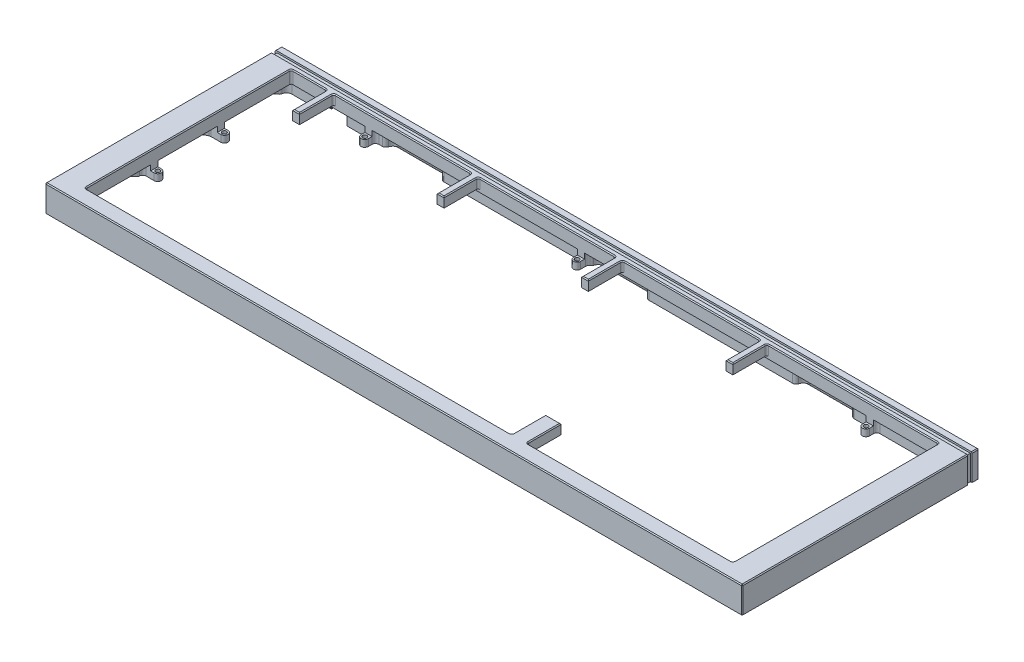
SolidWorks part; units mm, degrees
material "6061-T6 (SS)"
ref_plane "Front Plane" through (0, 0, 0) normal (0, 0, 1) x (1, 0, 0)
ref_plane "Top Plane" through (0, 0, 0) normal (0, 1, 0) x (1, 0, 0)
ref_plane "Right Plane" through (0, 0, 0) normal (1, 0, 0) x (0, 0, -1)
sketch "Sketch1" plane through (0, 0, 0) normal (0, 1, 0) x (1, 0, 0)
  line L1 (0, 0) -> (390.7, 0)
  line L2 (0, 0) -> (0, 132.7)
  line L3 (0, 132.7) -> (390.7, 132.7)
  line L4 (390.7, 0) -> (390.7, 132.7)
  line L5 (13.9, 124) -> (376.8, 124)
  line L6 (13.9, 124) -> (13.9, 8.7)
  line L7 (13.9, 8.7) -> (376.8, 8.7)
  line L8 (376.8, 124) -> (376.8, 8.7)
  point P9 (195.35, 124)
  point P10 (195.35, 132.7)
  point P11 (13.9, 66.35)
  point P12 (0, 66.35)
  dimension "D1" = 362.9
  dimension "D2" = 115.3
  dimension "D3" = 8.7
  dimension "D4" = 13.9
extrude "Main Body" add sketch "Sketch1" along normal blind 14.8
sketch "Sketch2" plane through (0, 0, 0) normal (0, -1, 0) x (1, 0, 0)
  line L0 (390.7, -132.7) -> (0, -132.7) construction
  line L1 (388.7, -130.7) -> (2, -130.7)
  line L2 (388.7, -130.7) -> (388.7, -2)
  line L3 (388.7, -2) -> (2, -2)
  line L4 (2, -130.7) -> (2, -2)
  line L5 (390.7, 0) -> (390.7, -132.7) construction
  point P4 (195.35, -130.7)
  point P7 (195.35, -132.7)
  point P8 (388.7, -66.35)
  point P11 (390.7, -66.35)
  dimension "D1" = 2
  dimension "D2" = 2
extrude "Alignment Guide" cut sketch "Sketch2" against normal blind 1 contours L2 L1 L4 L3
sketch "Sketch3" plane through (0, 14.8, 0) normal (0, 1, 0) x (1, 0, 0)
  line L0 (13.9, 8.7) -> (376.8, 8.7) construction
  line L1 (252.8, 27.8) -> (261.5, 27.8)
  line L2 (252.8, 27.8) -> (252.8, 8.7)
  line L3 (252.8, 8.7) -> (261.5, 8.7)
  line L4 (261.5, 27.8) -> (261.5, 8.7)
  line L5 (376.8, 8.7) -> (376.8, 124) construction
  line L6 (376.8, 124) -> (13.9, 124) construction
  line L7 (33.9, 124) -> (37.7, 124)
  line L8 (33.9, 124) -> (33.9, 104.9)
  line L9 (33.9, 104.9) -> (37.7, 104.9)
  line L10 (37.7, 124) -> (37.7, 104.9)
  line L11 (13.9, 124) -> (13.9, 8.7) construction
  line L12 (114.9, 124) -> (118.7, 124)
  line L13 (114.9, 124) -> (114.9, 104.9)
  line L14 (114.9, 104.9) -> (118.7, 104.9)
  line L15 (118.7, 124) -> (118.7, 104.9)
  line L16 (195.8, 124) -> (199.6, 124)
  line L17 (195.8, 124) -> (195.8, 104.9)
  line L18 (195.8, 104.9) -> (199.6, 104.9)
  line L19 (199.6, 124) -> (199.6, 104.9)
  line L20 (276.8, 124) -> (280.6, 124)
  line L21 (276.8, 124) -> (276.8, 104.9)
  line L22 (276.8, 104.9) -> (280.6, 104.9)
  line L23 (280.6, 124) -> (280.6, 104.9)
  point P8 (257.15, 8.7)
  dimension "D1" = 115.3
  dimension "D2" = 124
  dimension "D3" = 19.1
  dimension "D4" = 3.8
  dimension "D5" = 19.1
  dimension "D6" = 77.2
  dimension "D7" = 77.1
  dimension "D8" = 77.2
  dimension "D9" = 20
extrude "Blockers" add sketch "Sketch3" against normal blind 5.5
fillet "Fillet5" radius 1 14 edges at (280.6, 12.05, -124) (276.8, 12.05, -124) (195.8, 12.05, -124) (199.6, 12.05, -124) (118.7, 12.05, -124) (114.9, 12.05, -124) (33.9, 12.05, -124) (37.7, 12.05, -124) (13.9, 7.9, -124) (13.9, 7.9, -8.7) (252.8, 12.05, -8.7) (261.5, 12.05, -8.7) (376.8, 7.9, -8.7) (376.8, 7.9, -124)
sketch "Sketch4" plane through (0, 1, 0) normal (0, -1, 0) x (1, 0, 0)
  line L0 (0, 0) -> (390.7, 0) construction
  line L1 (381.25, -125.9) -> (9.45, -125.9)
  line L2 (381.25, -125.9) -> (381.25, -6.8)
  line L3 (381.25, -6.8) -> (9.45, -6.8)
  line L4 (9.45, -125.9) -> (9.45, -6.8)
  line L5 (390.7, 0) -> (390.7, -132.7) construction
  point P4 (195.35, -6.8)
  point P7 (195.35, 0)
  point P8 (381.25, -66.35)
  point P11 (390.7, -66.35)
  dimension "D1" = 119.1
  dimension "D2" = 371.8
extrude "PCB Cutout" cut sketch "Sketch4" against normal offset from surface (6.8 mm away) 7 up to face at (195.35, 14.8, -66.35)
fillet "Fillet4" radius 3 8 edges at (9.45, 4.4, -6.8) (9.45, 4.4, -125.9) (381.25, 4.4, -125.9) (381.25, 4.4, -6.8) (2, 0.5, -130.7) (2, 0.5, -2) (388.7, 0.5, -2) (388.7, 0.5, -130.7)
sketch "Sketch6" plane through (0, 1, 0) normal (0, -1, 0) x (1, 0, 0)
  line L0 (381.25, -9.8) -> (381.25, -122.9) construction
  line L1 (307.3, -127.1) -> (313.4, -127.1)
  line L2 (307.3, -127.1) -> (307.3, -125.9)
  line L3 (307.3, -125.9) -> (313.4, -125.9)
  line L4 (313.4, -127.1) -> (313.4, -125.9)
  line L5 (12.45, -125.9) -> (378.25, -125.9) construction
  line L11 (378.25, -6.8) -> (12.45, -6.8) construction
  line L16 (328.4, -6.8) -> (322.3, -6.8)
  line L17 (328.4, -6.8) -> (328.4, -4.8)
  line L18 (328.4, -4.8) -> (322.3, -4.8)
  line L19 (322.3, -6.8) -> (322.3, -4.8)
  line L20 (378.25, -125.9) -> (12.45, -125.9) construction
  line L21 (0, 0) -> (390.7, 0) construction
  line L22 (198.4, -127.1) -> (192.32, -127.1)
  line L23 (198.4, -127.1) -> (198.4, -125.9)
  line L24 (390.7, -66.35) -> (195.35, -66.35) construction
  line L25 (390.7, 0) -> (390.7, -132.7) construction
  line L26 (328.6755, -66.35) -> (328.6755, -130.7) construction
  line L27 (385.7, -130.7) -> (5, -130.7) construction
  line L28 (328.6755, -66.35) -> (328.6755, -8.7) construction
  line L29 (375.8, -8.7) -> (14.9, -8.7) construction
  line L53 (198.4, -125.9) -> (192.32, -125.9)
  line L54 (192.32, -127.1) -> (192.32, -125.9)
  line L55 (390.7, -132.7) -> (0, -132.7) construction
  line L56 (195.35, -132.7) -> (195.35, 0) construction
  line L57 (68.4, -6.8) -> (68.4, -4.8)
  line L58 (62.3, -4.8) -> (68.4, -4.8)
  line L59 (62.3, -6.8) -> (62.3, -4.8)
  line L60 (62.3, -6.8) -> (68.4, -6.8)
  line L61 (77.3, -127.1) -> (77.3, -125.9)
  line L62 (83.4, -125.9) -> (77.3, -125.9)
  line L63 (83.4, -127.1) -> (83.4, -125.9)
  line L64 (83.4, -127.1) -> (77.3, -127.1)
  line L65 (12.45, -6.8) -> (378.25, -6.8) construction
  line L66 (192.3, -4.8) -> (198.42, -4.8)
  line L67 (192.3, -4.8) -> (192.3, -6.8)
  line L68 (192.3, -6.8) -> (198.42, -6.8)
  line L69 (198.42, -4.8) -> (198.42, -6.8)
  line L70 (378.25, -6.8) -> (12.45, -6.8) construction
  line L75 (381.25, -122.9) -> (381.25, -9.8) construction
  line L76 (325.85, -125.9) -> (294.85, -125.9)
  line L77 (325.85, -125.9) -> (325.85, -130.15)
  line L78 (325.85, -130.15) -> (294.85, -130.15)
  line L79 (294.85, -125.9) -> (294.85, -130.15)
  line L80 (381.25, -122.35) -> (384.3, -122.35)
  line L81 (381.25, -122.35) -> (381.25, -90.35)
  line L82 (381.25, -90.35) -> (384.3, -90.35)
  line L83 (384.3, -122.35) -> (384.3, -90.35)
  line L84 (64.85, -130.15) -> (95.85, -130.15)
  line L85 (381.25, -10.35) -> (384.3, -10.35)
  line L86 (381.25, -10.35) -> (381.25, -42.35)
  line L87 (381.25, -42.35) -> (384.3, -42.35)
  line L88 (384.3, -10.35) -> (384.3, -42.35)
  line L89 (210.85, -125.9) -> (179.85, -125.9)
  line L90 (210.85, -125.9) -> (210.85, -130.15)
  line L91 (210.85, -130.15) -> (179.85, -130.15)
  line L92 (179.85, -125.9) -> (179.85, -130.15)
  line L97 (95.85, -125.9) -> (95.85, -130.15)
  line L98 (64.85, -125.9) -> (95.85, -125.9)
  line L99 (64.85, -125.9) -> (64.85, -130.15)
  line L100 (210.85, -125.9) -> (210.85, -130.15)
  line L101 (179.85, -125.9) -> (179.85, -130.15)
  line L102 (340.85, -6.8) -> (309.85, -6.8)
  line L108 (9.45, -42.35) -> (6.4, -42.35)
  line L109 (6.4, -10.35) -> (6.4, -42.35)
  line L110 (9.45, -10.35) -> (6.4, -10.35)
  line L111 (9.45, -10.35) -> (9.45, -42.35)
  line L112 (9.45, -90.35) -> (6.4, -90.35)
  line L113 (6.4, -122.35) -> (6.4, -90.35)
  line L114 (9.45, -122.35) -> (6.4, -122.35)
  line L115 (9.45, -122.35) -> (9.45, -90.35)
  line L116 (340.85, -6.8) -> (340.85, -2)
  line L117 (340.85, -2) -> (309.85, -2)
  line L118 (309.85, -6.8) -> (309.85, -2)
  line L119 (385.7, -2) -> (5, -2) construction
  line L120 (385.7, -2) -> (5, -2) construction
  line L121 (210.85, -6.8) -> (179.85, -6.8)
  line L122 (210.85, -6.8) -> (210.85, -2)
  line L123 (210.85, -2) -> (179.85, -2)
  line L124 (179.85, -6.8) -> (179.85, -2)
  line L125 (379.85, -49.5312) -> (374.82, -49.5312) construction
  line L126 (80.85, -6.8) -> (49.85, -6.8)
  line L127 (80.85, -6.8) -> (80.85, -2)
  line L128 (80.85, -2) -> (49.85, -2)
  line L129 (49.85, -6.8) -> (49.85, -2)
  line L130 (377.0547, -82.3692) -> (384.3, -82.3692)
  line L131 (377.0547, -82.3692) -> (377.0547, -49.5312)
  line L132 (377.0547, -49.5312) -> (384.3, -49.5312)
  line L133 (384.3, -82.3692) -> (384.3, -49.5312)
  line L134 (13.6453, -49.5312) -> (6.4, -49.5312)
  line L135 (6.4, -82.3692) -> (6.4, -49.5312)
  line L136 (13.6453, -82.3692) -> (6.4, -82.3692)
  line L137 (13.6453, -82.3692) -> (13.6453, -49.5312)
  line L138 (379.85, -82.3692) -> (374.82, -82.3692) construction
  circle A0 centre (381.25, -106.35) radius 3.05
  circle A1 centre (381.25, -26.35) radius 3.05
  circle A2 centre (325.35, -4.8) radius 3.05
  circle A3 centre (310.35, -127.1) radius 3.05
  circle A8 centre (65.35, -4.8) radius 3.05
  circle A9 centre (9.45, -26.35) radius 3.05
  circle A10 centre (9.45, -106.35) radius 3.05
  circle A11 centre (80.35, -127.1) radius 3.05
  circle A12 centre (195.35, -127.1) radius 3.05
  circle A13 centre (195.35, -4.8) radius 3.05
  point P25 (195.35, -66.35)
  point P93 (384.3, -26.35)
  point P94 (384.3, -106.35)
  point P95 (310.35, -130.15)
  point P100 (195.35, -130.15)
  point P102 (325.35, -2)
  point P113 (195.35, -2)
  point P126 (65.35, -2)
  dimension "D4" = 6.1
  dimension "D5" = 115
  dimension "D8" = 6.1
  dimension "D1" = 40
  dimension "D2" = 4.8
  dimension "D3" = 40
  dimension "D6" = 0
  dimension "D7" = 5.6
  dimension "D9" = 130
  dimension "D10" = 32
  dimension "D11" = 31
sketch "Sketch9" plane through (0, 0, -132.7) normal (0, 0, -1) x (-1, 0, 0)
  line L1 (-41.8, 0) -> (-29.8, 0)
  line L2 (-41.8, 0) -> (-41.8, 3.2)
  line L3 (-41.8, 3.2) -> (-29.8, 3.2)
  line L4 (-29.8, 0) -> (-29.8, 3.2)
  line L5 (-390.7, 0) -> (0, 0) construction
  line L7 (0, 14.8) -> (0, 0) construction
  point P6 (-35.8, 3.2)
  dimension "D1" = 3.2
  dimension "D3" = 12
  dimension "D4" = 35.8
extrude "USB Cutout" cut sketch "Sketch9" against normal up to surface (8.7 mm away) up to face at (164.87, 11.9, -124)
sketch "Sketch11" plane through (0, 0, -125.9) normal (0, 0, 1) x (1, 0, 0)
  line L0 (378.25, 7.8) -> (12.45, 7.8) construction
  line L1 (43.3, 1) -> (28.3, 1)
  line L2 (43.3, 1) -> (43.3, 7.8)
  line L3 (43.3, 7.8) -> (28.3, 7.8)
  line L4 (28.3, 1) -> (28.3, 7.8)
  line L7 (12.45, 1) -> (29.8, 1) construction
  line L8 (29.8, 3.2) -> (41.8, 3.2) construction
  point P8 (35.8, 1)
  point P18 (35.8, 3.2)
  dimension "D1" = 15
extrude "PCB Clearance" cut sketch "Sketch11" against normal blind 3.9
fillet "Fillet7" radius 2.5 2 edges at (28.3, 4.4, -129.8) (43.3, 4.4, -129.8)
chamfer "Chamfer1" distance 0.5 46 edges at (14.1929, 14.8, -8.9929) (133.35, 14.8, -8.7) (252.5071, 14.8, -8.9929) (252.8, 14.8, -18.75) (257.15, 14.8, -27.8) (261.5, 14.8, -18.75) (261.7929, 14.8, -8.9929) (319.15, 14.8, -8.7) (376.5071, 14.8, -8.9929) (376.8, 14.8, -66.35) (376.5071, 14.8, -123.7071) (328.7, 14.8, -124) (280.8929, 14.8, -123.7071) (280.6, 14.8, -113.95) (278.7, 14.8, -104.9) (276.8, 14.8, -113.95) (276.5071, 14.8, -123.7071) (238.2, 14.8, -124) (199.8929, 14.8, -123.7071) (199.6, 14.8, -113.95) (197.7, 14.8, -104.9) (195.8, 14.8, -113.95) (195.5071, 14.8, -123.7071) (157.25, 14.8, -124) (118.9929, 14.8, -123.7071) (118.7, 14.8, -113.95) (116.8, 14.8, -104.9) (114.9, 14.8, -113.95) (114.6071, 14.8, -123.7071) (76.3, 14.8, -124) (37.9929, 14.8, -123.7071) (37.7, 14.8, -113.95) (35.8, 14.8, -104.9) (33.9, 14.8, -113.95) (33.6071, 14.8, -123.7071) (23.9, 14.8, -124) (14.1929, 14.8, -123.7071) (13.9, 14.8, -66.35) (195.35, 14.8, -132.7) (390.7, 14.8, -66.35) (195.35, 14.8, 0) (0, 14.8, -66.35) (390.7, 7.4, -132.7) (390.7, 7.4, 0) (0, 7.4, -132.7) (0, 7.4, 0)
chamfer "Chamfer2" distance 0.1 5 edges at (390.7, 0, -66.35) (195.35, 0, 0) (0, 0, -66.35) (15.15, 0, -132.7) (216, 0, -132.7)
sketch "Sketch27" plane through (0, 14.8, 0) normal (0, 1, 0) x (1, 0, 0)
  line L0 (0, 0.5) -> (0, 132.2) construction
  line L1 (0, 128.95) -> (390.7, 128.95)
  line L2 (0, 128.95) -> (0, 126.45)
  line L3 (0, 126.45) -> (390.7, 126.45)
  line L4 (390.7, 128.95) -> (390.7, 126.45)
  line L5 (390.7, 132.2) -> (390.7, 0.5) construction
  line L6 (372.9261, 132.2) -> (372.9261, 124.5) construction
  line L7 (390.2, 132.2) -> (0.5, 132.2) construction
  line L9 (281.6, 124.5) -> (375.8, 124.5) construction
  point P14 (390.7, 127.7)
  dimension "D1" = 2.5
  dimension "D2" = 3.2
extrude "Cut-Extrude11" cut sketch "Sketch27" against normal blind 1
sketch "Sketch28" plane through (0, 13.8, 0) normal (0, 1, 0) x (1, 0, 0)
  line L1 (0, 128.95) -> (1, 128.95)
  line L2 (0, 128.95) -> (0, 126.45)
  line L3 (0, 126.45) -> (1, 126.45)
  line L4 (1, 128.95) -> (1, 126.45)
  line L5 (389.7, 128.95) -> (390.7, 128.95)
  line L6 (389.7, 128.95) -> (389.7, 126.45)
  line L7 (389.7, 126.45) -> (390.7, 126.45)
  line L8 (390.7, 128.95) -> (390.7, 126.45)
  line L9 (390.7, 128.95) -> (0, 128.95) construction
  line L10 (0, 126.45) -> (390.7, 126.45) construction
  dimension "D1" = 1
  dimension "D2" = 1
extrude "Cut-Extrude12" cut sketch "Sketch28" against normal through all
sketch "Sketch21" [suppressed] plane through (0, 14.8, 0) normal (0, 1, 0) x (1, 0, 0)
  line L0 (0.5, 132.7) -> (390.24, 132.7) construction
  line L1 (382.53, 132.7) -> (385.03, 132.7)
  line L2 (382.53, 132.7) -> (382.53, 72.7)
  line L3 (382.53, 72.7) -> (385.03, 72.7)
  line L4 (385.03, 132.7) -> (385.03, 72.7)
  line L5 (390.74, 132.2) -> (390.74, 129.7) construction
  line L6 (390.74, 129.1) -> (294.74, 129.1)
  line L7 (390.74, 129.1) -> (390.74, 127.6)
  line L8 (390.74, 127.6) -> (294.74, 127.6)
  line L9 (294.74, 129.1) -> (294.74, 127.6)
  line L10 (362.9081, 132.2) -> (362.9081, 124.5) construction
  line L11 (390.24, 132.2) -> (0.5, 132.2) construction
  line L12 (281.62, 124.5) -> (375.82, 124.5) construction
  line L13 (365.5702, 129.1) -> (365.5702, 127.6) construction
  line L14 (377.32, 119.5259) -> (390.24, 119.5259) construction
  line L15 (377.32, 123) -> (377.32, 9.7) construction
  line L16 (390.24, 0.5) -> (390.24, 127.2) construction
  line L17 (382.53, 116.0504) -> (385.03, 116.0504) construction
  point P28 (383.78, 116.0504)
  point P29 (383.78, 119.5259)
  point P30 (365.5702, 128.35)
  point P31 (362.9081, 128.35)
  dimension "D1" = 2.5
  dimension "D2" = 1.5
  dimension "D3" = 60
  dimension "D4" = 96
extrude "Cut-Extrude5" [suppressed] cut sketch "Sketch21" against normal blind 1 contours L4 L3 L2 L1 | L8 L9 L6 L7
sketch "Sketch23" [suppressed] plane through (390.74, 0, 0) normal (1, 0, 0) x (0, 0, -1)
  line L0 (129.1, 13.8) -> (129.1, 14.3) construction
  line L1 (127.6, 13.8) -> (129.1, 13.8)
  line L2 (127.6, 13.8) -> (127.6, 0)
  line L3 (127.6, 0) -> (129.1, 0)
  line L4 (129.1, 13.8) -> (129.1, 0)
extrude "Cut-Extrude6" [suppressed] cut sketch "Sketch23" against normal blind 1
sketch "Sketch19" plane through (0, 14.8, 0) normal (0, 1, 0) x (1, 0, 0)
  line L0 (0.5, 132.7) -> (390.2, 132.7) construction
  line L1 (5.45, 132.7) -> (8.45, 132.7)
  line L2 (5.45, 132.7) -> (5.45, 0)
  line L3 (5.45, 0) -> (8.45, 0)
  line L4 (8.45, 132.7) -> (8.45, 0)
  line L7 (382.25, 132.7) -> (385.25, 132.7)
  line L8 (382.25, 132.7) -> (382.25, 0)
  line L9 (382.25, 0) -> (385.25, 0)
  line L10 (385.25, 132.7) -> (385.25, 0)
  line L11 (390.2, 0) -> (0.5, 0) construction
  line L12 (377.3, 110.209) -> (390.2, 110.209) construction
  line L13 (377.3, 123) -> (377.3, 9.7) construction
  line L14 (390.2, 0.5) -> (390.2, 126.45) construction
  line L15 (382.25, 106.8719) -> (385.25, 106.8719) construction
  line L16 (0.5, 106.8719) -> (13.4, 106.8719) construction
  line L17 (0.5, 132.2) -> (0.5, 128.95) construction
  line L18 (13.4, 9.7) -> (13.4, 123) construction
  line L19 (5.45, 102.7297) -> (8.45, 102.7297) construction
  point P12 (383.75, 106.8719)
  point P14 (383.75, 110.209)
  point P30 (6.95, 102.7297)
  point P31 (6.95, 106.8719)
  dimension "D1" = 3
  dimension "D2" = 3
extrude "Cut-Extrude3" [suppressed] cut sketch "Sketch19" against normal blind 1
sketch "Sketch17" plane through (0, 14.8, 0) normal (0, 1, 0) x (1, 0, 0)
  line L0 (390.2, 0.5) -> (390.2, 126.45) construction
  line L1 (5.7, 129.6) -> (385, 129.6)
  line L2 (5.7, 129.6) -> (5.7, -2.65)
  line L3 (5.7, -2.65) -> (385, -2.65)
  line L4 (385, 129.6) -> (385, -2.65)
  line L5 (8.2, 127.1) -> (382.5, 127.1)
  line L6 (8.2, 127.1) -> (8.2, -0.15)
  line L7 (8.2, -0.15) -> (382.5, -0.15)
  line L8 (382.5, 127.1) -> (382.5, -0.15)
  line L9 (390.2, 132.2) -> (0.5, 132.2) construction
  line L10 (21.2533, 132.2) -> (21.2533, 124.5) construction
  line L11 (14.9, 124.5) -> (32.9, 124.5) construction
  line L12 (25.2757, 129.6) -> (25.2757, 127.1) construction
  line L13 (0.5, 116.1326) -> (13.4, 116.1326) construction
  line L14 (0.5, 132.2) -> (0.5, 128.95) construction
  line L15 (13.4, 9.7) -> (13.4, 123) construction
  line L16 (5.7, 120.1548) -> (8.2, 120.1548) construction
  point P8 (382.5, 63.475)
  point P9 (385, 63.475)
  point P12 (390.2, 63.475)
  point P13 (195.35, 129.6)
  point P14 (195.35, 127.1)
  point P17 (195.35, 132.2)
  point P24 (25.2757, 128.35)
  point P25 (21.2533, 128.35)
  point P34 (6.95, 116.1326)
  point P35 (6.95, 120.1548)
  dimension "D1" = 2.5
  dimension "D2" = 2.5
extrude "Cut-Extrude1" [suppressed] cut sketch "Sketch17" against normal blind 1
fillet "Fillet8" radius 0.1 9 edges at (213.75, 0, -130.7) (387.8213, 0, -129.8213) (17.4, 0, -130.7) (2.8787, 0, -129.8213) (2, 0, -66.35) (2.8787, 0, -2.8787) (195.35, 0, -2) (387.8213, 0, -2.8787) (388.7, 0, -66.35)
sketch "Sketch32" plane through (0, 1, 0) normal (0, -1, 0) x (1, 0, 0)
  line L0 (378.25, -125.9) -> (43.3, -125.9) construction
  line L3 (378.25, -125.9) -> (43.3, -125.9) construction
  line L4 (340.2441, -121.9) -> (336.2441, -121.9)
  line L5 (340.2441, -121.9) -> (340.2441, -125.9)
  line L6 (340.2441, -125.9) -> (336.2441, -125.9)
  line L7 (336.2441, -121.9) -> (336.2441, -125.9)
  line L9 (178.3191, -121.9) -> (174.3191, -121.9)
  line L10 (178.3191, -121.9) -> (178.3191, -125.9)
  line L11 (178.3191, -125.9) -> (174.3191, -125.9)
  line L12 (174.3191, -121.9) -> (174.3191, -125.9)
  line L13 (43.3, -125.9) -> (378.25, -125.9) construction
  line L14 (59.2566, -121.9) -> (55.2566, -121.9)
  line L15 (59.2566, -121.9) -> (59.2566, -125.9)
  line L16 (59.2566, -125.9) -> (55.2566, -125.9)
  line L17 (55.2566, -121.9) -> (55.2566, -125.9)
  line L18 (9.45, -9.8) -> (9.45, -122.9) construction
  line L19 (15.88, -82.6192) -> (9.45, -82.6192)
  line L20 (15.88, -82.6192) -> (15.88, -86.6192)
  line L21 (15.88, -86.6192) -> (9.45, -86.6192)
  line L22 (9.45, -82.6192) -> (9.45, -86.6192)
  line L23 (12.45, -6.8) -> (378.25, -6.8) construction
  line L24 (15.88, -45.2812) -> (9.45, -45.2812)
  line L25 (15.88, -45.2812) -> (15.88, -49.2812)
  line L26 (15.88, -49.2812) -> (9.45, -49.2812)
  line L27 (9.45, -45.2812) -> (9.45, -49.2812)
  line L28 (87.8316, -11.6) -> (83.8316, -11.6)
  line L29 (87.8316, -11.6) -> (87.8316, -6.8)
  line L30 (87.8316, -6.8) -> (83.8316, -6.8)
  line L31 (83.8316, -11.6) -> (83.8316, -6.8)
  line L32 (378.25, -6.8) -> (12.45, -6.8) construction
  line L33 (158.5, -11.6) -> (154.5, -11.6)
  line L34 (158.5, -11.6) -> (158.5, -6.8)
  line L35 (158.5, -6.8) -> (154.5, -6.8)
  line L36 (154.5, -11.6) -> (154.5, -6.8)
  line L37 (378.25, -6.8) -> (12.45, -6.8) construction
  line L38 (302.2, -11.6) -> (298.2, -11.6)
  line L39 (302.2, -11.6) -> (302.2, -6.8)
  line L40 (302.2, -6.8) -> (298.2, -6.8)
  line L41 (298.2, -11.6) -> (298.2, -6.8)
  line L42 (195.35, 0) -> (195.35, -132.6) construction
  line L43 (0.5, 0) -> (390.2, 0) construction
  line L44 (381.25, -45.2812) -> (381.25, -49.2812)
  line L45 (374.82, -49.2812) -> (381.25, -49.2812)
  line L46 (374.82, -45.2812) -> (374.82, -49.2812)
  line L47 (374.82, -45.2812) -> (381.25, -45.2812)
  line L48 (381.25, -82.6192) -> (381.25, -86.6192)
  line L49 (374.82, -86.6192) -> (381.25, -86.6192)
  line L50 (374.82, -82.6192) -> (374.82, -86.6192)
  line L51 (374.82, -82.6192) -> (381.25, -82.6192)
  line L52 (41.8, -132.6) -> (390.3, -132.6) construction
  circle A0 centre (338.2441, -121.9) radius 2
  circle A1 centre (176.3191, -121.9) radius 2
  circle A2 centre (57.2566, -121.9) radius 2
  circle A3 centre (15.88, -84.6192) radius 2
  circle A4 centre (15.88, -47.2812) radius 2
  circle A5 centre (85.8316, -11.6) radius 2
  circle A6 centre (156.5, -11.6) radius 2
  circle A7 centre (300.2, -11.6) radius 2
  circle A8 centre (374.82, -47.2812) radius 2
  circle A9 centre (374.82, -84.6192) radius 2
  dimension "D1" = 4
extrude "Boss-Extrude1" add sketch "Sketch32" against normal offset from surface (3.8 mm away) 3 contours A1 | L12 L11 L10 L9 | A0 | L5 L6 L7 L4 | A9 | L51 L48 L49 L50 | L47 L44 L45 L46 | A8 | L41 L40 L39 L38 | A7 | A5 | L31 L30 L29 L28 | A4 | L26 L27 L24 L25 | A3 | L19 L22 L21 L20 | A2 | L15 L16 L17 L14 up to face at (126.9714, 7.8, -92.7025)
sketch "Sketch33" plane through (0, 7.8, 0) normal (0, -1, 0) x (1, 0, 0)
  line L0 (374.82, -82.6192) -> (381.25, -82.6192) construction
  line L1 (381.25, -86.6192) -> (376.8, -86.6192)
  line L2 (381.25, -86.6192) -> (381.25, -82.6192)
  line L3 (381.25, -82.6192) -> (376.8, -82.6192)
  line L4 (376.8, -86.6192) -> (376.8, -82.6192)
  line L5 (376.8, -123) -> (376.8, -9.7) construction
  line L6 (374.82, -45.2812) -> (381.25, -45.2812) construction
  line L7 (381.25, -49.2812) -> (376.8, -49.2812)
  line L8 (381.25, -49.2812) -> (381.25, -45.2812)
  line L9 (381.25, -45.2812) -> (376.8, -45.2812)
  line L10 (376.8, -49.2812) -> (376.8, -45.2812)
  line L11 (375.8, -8.7) -> (14.9, -8.7) construction
  line L12 (302.2, -6.8) -> (298.2, -6.8)
  line L13 (302.2, -6.8) -> (302.2, -8.7)
  line L14 (302.2, -8.7) -> (298.2, -8.7)
  line L15 (298.2, -6.8) -> (298.2, -8.7)
  line L16 (298.2, -11.6) -> (298.2, -6.8) construction
  line L22 (83.8316, -11.6) -> (83.8316, -6.8) construction
  line L23 (87.8316, -6.8) -> (83.8316, -6.8)
  line L24 (87.8316, -6.8) -> (87.8316, -8.7)
  line L25 (87.8316, -8.7) -> (83.8316, -8.7)
  line L26 (83.8316, -6.8) -> (83.8316, -8.7)
  line L27 (15.88, -49.2812) -> (9.45, -49.2812) construction
  line L28 (9.45, -45.2812) -> (13.9, -45.2812)
  line L29 (9.45, -45.2812) -> (9.45, -49.2812)
  line L30 (9.45, -49.2812) -> (13.9, -49.2812)
  line L31 (13.9, -45.2812) -> (13.9, -49.2812)
  line L32 (13.9, -9.7) -> (13.9, -123) construction
  line L33 (15.88, -86.6192) -> (9.45, -86.6192) construction
  line L34 (9.45, -82.6192) -> (13.9, -82.6192)
  line L35 (9.45, -82.6192) -> (9.45, -86.6192)
  line L36 (9.45, -86.6192) -> (13.9, -86.6192)
  line L37 (13.9, -82.6192) -> (13.9, -86.6192)
  line L38 (59.2566, -121.9) -> (59.2566, -125.9) construction
  line L39 (55.2566, -125.9) -> (59.2566, -125.9)
  line L40 (55.2566, -125.9) -> (55.2566, -124)
  line L41 (55.2566, -124) -> (59.2566, -124)
  line L42 (59.2566, -125.9) -> (59.2566, -124)
  line L43 (14.9, -124) -> (375.8, -124) construction
  line L44 (178.3191, -121.9) -> (178.3191, -125.9) construction
  line L45 (174.3191, -125.9) -> (178.3191, -125.9)
  line L46 (174.3191, -125.9) -> (174.3191, -124)
  line L47 (174.3191, -124) -> (178.3191, -124)
  line L48 (178.3191, -125.9) -> (178.3191, -124)
  line L49 (340.2441, -121.9) -> (340.2441, -125.9) construction
  line L50 (336.2441, -125.9) -> (340.2441, -125.9)
  line L51 (336.2441, -125.9) -> (336.2441, -124)
  line L52 (336.2441, -124) -> (340.2441, -124)
  line L53 (340.2441, -125.9) -> (340.2441, -124)
extrude "Boss-Extrude2" add sketch "Sketch33" along normal up to surface (3 mm away) up to face at (338.2441, 4.8, -123.4)
sketch "Sketch34" plane through (0, 4.8, 0) normal (0, 1, 0) x (1, 0, 0)
  point P0 (15.88, 47.2812)
  point P1 (15.88, 84.6192)
  point P3 (85.8316, 11.6)
  point P7 (300.2, 11.6)
  point P9 (374.82, 47.2812)
  point P11 (374.82, 84.6192)
  point P13 (338.2441, 121.9)
  point P15 (176.3191, 121.9)
  point P17 (57.2566, 121.9)
  point P19 (0, 0)
hole_wizard "M2 Clearance Hole1" positions "3DSketch4" profile "Sketch35" hole size "M2" standard "ANSI Metric" end condition through all
sketch3d "3DSketch4"
  point P0 (57.2566, 4.8, -121.9)
  point P3 (15.88, 4.8, -84.6192)
  point P6 (15.88, 4.8, -47.2812)
  point P9 (85.8316, 4.8, -11.6)
  point P15 (300.2, 4.8, -11.6)
  point P18 (374.82, 4.8, -47.2812)
  point P21 (374.82, 4.8, -84.6192)
  point P24 (338.2441, 4.8, -121.9)
  point P27 (176.3191, 4.8, -121.9)
  point P30 (0, 0, 0)
sketch "Sketch35" plane through (57.2566, 4.8, -121.9) normal (1, 0, 0) x (0, 0, 1)
  line L0 (0, 0) -> (0, 4.8)
  line L1 (0, 4.8) -> (1.2, 4.8)
  line L2 (1.2, 4.8) -> (1.2, 0)
  line L5 (1.2, 0) -> (0, 0)
  line L11 (0, -6.35) -> (0, 107.95) construction
  dimension "Thru Hole Dia." = 2.4
  dimension "Thru Hole Depth" = 4.8
extrude "Cut-Extrude13" cut sketch "Sketch6" against normal up to surface (6.8 mm away) contours L77 L76 L79 L78 | L81 L80 L83 L82 | L86 L85 L88 L87 | L102 L118 L117 L116 | L108 L109 L110 L111 | L112 L113 L114 L115 | L84 L97 L98 L99 | L90 L89 L92 L91 | L121 L124 L123 L122 | L126 L129 L128 L127 | L133 L132 L131 L130 | L135 L134 L137 L136 up to face at (257.2816, 7.8, -124.95)
fillet "Fillet10" radius 4 24 edges at (210.85, 4.4, -2) (80.85, 4.4, -2) (49.85, 4.4, -2) (6.4, 4.4, -10.35) (6.4, 4.4, -42.35) (6.4, 4.4, -90.35) (6.4, 4.4, -122.35) (64.85, 4.4, -130.15) (95.85, 4.4, -130.15) (210.85, 4.4, -130.15) (179.85, 4.4, -130.15) (294.85, 4.4, -130.15) (325.85, 4.4, -130.15) (384.3, 4.4, -42.35) (384.3, 4.4, -10.35) (384.3, 4.4, -90.35) (384.3, 4.4, -122.35) (340.85, 4.4, -2) (309.85, 4.4, -2) (179.85, 4.4, -2) (6.4, 4.4, -82.3692) (6.4, 4.4, -49.5312) (384.3, 4.4, -82.3692) (384.3, 4.4, -49.5312)
fillet "Fillet11" radius 2 20 edges at (381.25, 4.4, -90.35) (381.25, 4.4, -122.35) (325.85, 4.4, -125.9) (294.85, 4.4, -125.9) (179.85, 4.4, -125.9) (210.85, 4.4, -125.9) (95.85, 4.4, -125.9) (64.85, 4.4, -125.9) (9.45, 4.4, -122.35) (9.45, 4.4, -90.35) (9.45, 4.4, -42.35) (9.45, 4.4, -10.35) (49.85, 4.4, -6.8) (80.85, 4.4, -6.8) (179.85, 4.4, -6.8) (210.85, 4.4, -6.8) (309.85, 4.4, -6.8) (340.85, 4.4, -6.8) (381.25, 4.4, -10.35) (381.25, 4.4, -42.35)
fillet "Fillet9" radius 1.9 18 edges at (340.2441, 4.4, -125.9) (336.2441, 4.4, -125.9) (174.3191, 4.4, -125.9) (59.2566, 4.4, -125.9) (55.2566, 4.4, -125.9) (9.45, 4.4, -86.6192) (9.45, 4.4, -82.6192) (9.45, 4.4, -45.2812) (9.45, 4.4, -49.2812) (87.8316, 4.4, -6.8) (83.8316, 4.4, -6.8) (302.2, 4.4, -6.8) (298.2, 4.4, -6.8) (381.25, 4.4, -45.2812) (381.25, 4.4, -49.2812) (381.25, 4.4, -86.6192) (381.25, 4.4, -82.6192) (178.3191, 4.4, -125.9)
sketch "Sketch36" plane through (0, 7.8, 0) normal (0, -1, 0) x (-1, 0, 0)
  line L0 (-298.85, 130.15) -> (-321.85, 130.15) construction
  line L1 (-376.8, 123) -> (-376.8, 86.6192) construction
  line L2 (-384.3, 94.2356) -> (-384.3, 118.4644) construction
  line L3 (-313.85, 2) -> (-336.85, 2) construction
  line L4 (-195.35, 130.15) -> (-195.35, 2) construction
  line L5 (-183.85, 130.15) -> (-206.85, 130.15) construction
  line L6 (-183.85, 2) -> (-206.85, 2) construction
  line L7 (-178.3191, 124) -> (-336.2441, 124) construction
  line L8 (-384.3, 38.4644) -> (-384.3, 14.2356) construction
  line L9 (-375.8, 8.7) -> (-302.2, 8.7) construction
  line L10 (-384.3, 78.4836) -> (-384.3, 53.4167) construction
  point P0 (-381.1, 26.35)
  point P1 (-325.35, 5)
  point P2 (-195.35, 5)
  point P3 (-195.35, 127.15)
  point P4 (-310.35, 127.15)
  point P5 (-381.1, 106.35)
  point P9 (-325.35, 2)
  point P24 (-310.35, 130.15)
  point P27 (-384.3, 26.35)
  point P29 (-384.3, 106.35)
  point P30 (-65.35, 5)
  point P31 (-9.6, 26.35)
  point P32 (-9.6, 106.35)
  point P33 (-80.35, 127.15)
  point P34 (-381.1, 65.9502)
  point P38 (-384.3, 65.9502)
  point P41 (-9.6, 65.9502)
  dimension "D1" = 3.15
  dimension "D2" = 4.3
  dimension "D3" = 3.7
hole_wizard "M2x0.4 Tapped Hole1" positions "3DSketch5" profile "Sketch37" tap size "M2x0.4" standard "ANSI Metric"
sketch3d "3DSketch5"
  point P0 (381.1, 7.8, -106.35)
  point P3 (381.1, 7.8, -26.35)
  point P6 (325.35, 7.8, -5)
  point P9 (310.35, 7.8, -127.15)
  point P12 (195.35, 7.8, -5)
  point P15 (195.35, 7.8, -127.15)
  point P18 (80.35, 7.8, -127.15)
  point P21 (65.35, 7.8, -5)
  point P24 (9.6, 7.8, -26.35)
  point P27 (9.6, 7.8, -106.35)
  point P30 (381.1, 7.8, -65.9502)
  point P33 (9.6, 7.8, -65.9502)
sketch "Sketch37" plane through (381.1, 7.8, -106.35) normal (1, 0, 0) x (0, 0, -1)
  line L0 (0, 0) -> (0, 4.4807)
  line L1 (0, 4.4807) -> (0.8, 4)
  line L2 (0.8, 4) -> (0.8, 0)
  line L5 (0.8, 0) -> (0, 0)
  line L10 (0, 4.4807) -> (-0.8, 4) construction
  line L11 (0, -6.35) -> (0, 107.95) construction
  dimension "Tap Drill Dia." = 1.6
  dimension "Tap Drill Depth" = 4
  dimension "Drill Angle" = 118
cosmetic thread "Hole Thread1" parameters "D1"=4, "D2"=2
cosmetic thread "Hole Thread2" parameters "D1"=4, "D2"=2
cosmetic thread "Hole Thread3" parameters "D1"=4, "D2"=2
cosmetic thread "Hole Thread4" parameters "D1"=4, "D2"=2
cosmetic thread "Hole Thread5" parameters "D1"=4, "D2"=2
cosmetic thread "Hole Thread6" parameters "D1"=4, "D2"=2
cosmetic thread "Hole Thread7" parameters "D1"=4, "D2"=2
cosmetic thread "Hole Thread8" parameters "D1"=4, "D2"=2
cosmetic thread "Hole Thread9" parameters "D1"=4, "D2"=2
cosmetic thread "Hole Thread10" parameters "D1"=4, "D2"=2
cosmetic thread "Hole Thread11" parameters "D1"=4, "D2"=2
cosmetic thread "Hole Thread12" parameters "D1"=4, "D2"=2
